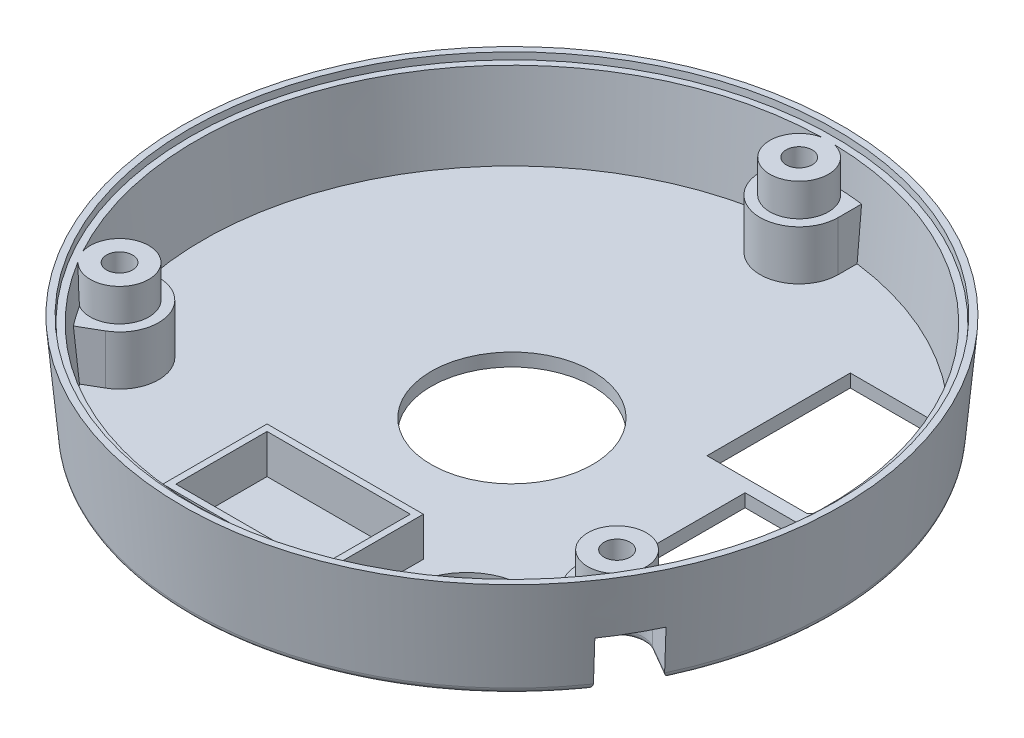
SolidWorks part; units mm, degrees
ref_plane "前视基准面" through (0, 0, 0) normal (0, 0, 1) x (1, 0, 0)
ref_plane "上视基准面" through (0, 0, 0) normal (0, 1, 0) x (1, 0, 0)
ref_plane "右视基准面" through (0, 0, 0) normal (1, 0, 0) x (0, 0, -1)
sketch "草图7" plane through (0, 0, 0) normal (0, 0, 1) x (1, 0, 0)
  line L0 (0, 0) -> (24.6, 0)
  line L1 (24.6, 0) -> (25.3, 7.8)
  line L2 (25.3, 7.8) -> (24.8, 7.8)
  line L3 (24.2551, 7.3) -> (23.6897, 1)
  line L4 (23.6897, 1) -> (0, 1)
  line L5 (0, 1) -> (0, 0)
  line L6 (24.8, 7.8) -> (24.7551, 7.3)
  line L7 (24.7551, 7.3) -> (24.2551, 7.3)
  dimension "D1" = 24.6
  dimension "D2" = 25.3
  dimension "D4" = 1
  dimension "D5" = 7.8
  dimension "D6" = 0.5
revolve "旋转1" add sketch "草图7" angle 360 about L5
sketch "草图8" plane through (0, 1, 0) normal (0, 1, 0) x (1, 0, 0)
  line L0 (-3, 22.05) -> (-3, 24.1141)
  line L1 (0, 22.05) -> (-19.0959, -11.025) construction
  line L2 (-19.0959, -11.025) -> (19.0959, -11.025) construction
  line L3 (19.0959, -11.025) -> (0, 22.05) construction
  line L4 (3, 22.05) -> (3, 24.1141)
  circle A0 centre (0, 0) radius 11.025 construction
  circle A1 centre (0, 22.05) radius 1
  circle A2 centre (0, 22.05) radius 2.25
  arc A3 (-3, 22.05) -> (3, 22.05) centre (0, 22.05) ccw
  circle A4 centre (0, 0) radius 24.3 construction
  arc A6 (-3, 24.1141) -> (3, 24.1141) centre (0, 0) cw
  dimension "D1" = 2
  dimension "D2" = 4.5
  dimension "D3" = 6
extrude "凸台-拉伸23" add sketch "草图8" along normal up to surface (6.3 mm away) contours A2 up to face at (-24.2551, 7.3, 0)
extrude "凸台-拉伸24" add sketch "草图8<4>" along normal blind 3.8 contours A6 L4 A3 L0
sketch "草图8<4>" plane through (0, 1, 0) normal (0, 1, 0) x (1, 0, 0) same geometry as "草图8"
extrude "切除-拉伸2" cut sketch "草图8<5>" against normal through all both and the other way through all contours A1
sketch "草图8<5>" plane through (0, 1, 0) normal (0, 1, 0) x (1, 0, 0) same geometry as "草图8"
pattern_circular "阵列(圆周)1" count 3 over 360 about axis through (0, 1, 0) along (0, 1, 0) of "凸台-拉伸23", "凸台-拉伸24", "切除-拉伸2"
sketch "草图9" plane through (0, 0, 0) normal (0, -1, 0) x (1, 0, 0)
  line L0 (2, -22.05) -> (2, -26.0952)
  line L1 (2, -26.0952) -> (-2, -26.0952)
  line L2 (-2, -26.0952) -> (-2, -22.05)
  arc A0 (2, -22.05) -> (-2, -22.05) centre (0, -22.05) ccw
  dimension "D1" = 4
extrude "切除-拉伸3" cut sketch "草图9" against normal blind 3.7 contours L2 A0 L0 L1
pattern_circular "阵列(圆周)2" count 3 over 360 about axis through (0, 0, 0) along (0, 1, 0) of "切除-拉伸3"
sketch "草图11" plane through (0, 1, 0) normal (0, 1, 0) x (1, 0, 0)
  line L0 (0, 0) -> (0, 22.05) construction
  line L1 (10, 15.975) -> (10, 4.975)
  line L2 (10, 4.975) -> (17.7, 4.975)
  line L4 (18.7, 5.975) -> (18.7, 14.975)
  line L6 (17.7, 15.975) -> (10, 15.975)
  line L7 (10, 15.975) -> (10, 21.4757) construction
  line L8 (13.9242, 3.975) -> (13.9242, -7.025)
  line L9 (13.9242, -7.025) -> (21.6242, -7.025)
  line L10 (22.6242, -6.025) -> (22.6242, 2.975)
  line L11 (21.6242, 3.975) -> (13.9242, 3.975)
  line L12 (19.0959, -8.025) -> (9.5, -8.025) construction
  line L15 (21.6242, -7.025) -> (22.6242, -6.025)
  line L16 (22.6242, 2.975) -> (21.6242, 3.975)
  line L17 (17.7, 4.975) -> (18.7, 5.975)
  line L18 (18.7, 14.975) -> (17.7, 15.975)
  arc A1 (21.8507, -9.1514) -> (3, 23.499) centre (0, 0) ccw construction
  arc A2 (20.5959, -8.4269) -> (17.5959, -13.6231) centre (19.0959, -11.025) ccw construction
  point P6 (22.6242, -7.025)
  point P7 (22.6242, 3.975)
  point P8 (0, 0)
  point P9 (0, 0)
  point P10 (18.7, 15.975)
  point P21 (18.7, 4.975)
  dimension "D1" = 10
  dimension "D2" = 8.7
  dimension "D3" = 11
  dimension "D4" = 1
  dimension "D5" = 1
  dimension "D7" = 8.7
  dimension "D8" = 11
extrude "切除-拉伸6" cut sketch "草图11" against normal up to surface (1 mm away) up to face at (0, 0, 0)
sketch "草图12" plane through (0, 1, 0) normal (0, 1, 0) x (1, 0, 0)
  line L0 (-5.5, -13.3) -> (-5.5, -20.3)
  line L1 (-5.5, -20.3) -> (5.5, -20.3)
  line L2 (5.5, -20.3) -> (5.5, -13.3)
  line L3 (5.5, -13.3) -> (-5.5, -13.3)
  line L4 (-18.1727, -25.3) -> (19.526, -25.3) construction
  circle A1 centre (0, 0) radius 25.3 construction
  point P3 (0, -13.3)
  dimension "D1" = 12
  dimension "D2" = 5
  dimension "D3" = 11
extrude "拉伸-薄壁1" add sketch "草图12" along normal blind 3 thin thin type one direction wall 0.5
sketch "草图13" plane through (0, 0, 0) normal (0, -1, 0) x (-1, 0, 0)
  line L0 (24.6, 19.236) -> (24.6, -17.3672) construction
  line L1 (6.6, 23.6981) -> (6.6, -23.6981) construction
  arc A0 (22.2337, -10.5272) -> (2, 24.5186) centre (0, 0) ccw construction
  arc A1 (-20.2337, -13.9913) -> (20.2337, -13.9913) centre (0, 0) ccw construction
  dimension "D1" = 18
sketch "草图14" plane through (0, 1, 0) normal (0, 1, 0) x (1, 0, 0)
  circle A0 centre (0, 0) radius 11.7 construction
  circle A2 centre (0, 0) radius 6.2
  circle A3 centre (11.7077, -15.2045) radius 4.5
  arc A4 (-18.8507, -14.3476) -> (18.8507, -14.3476) centre (0, 0) ccw construction
  point P6 (10.9576, -12.2246)
  point P7 (11.6858, -15.1761)
  dimension "D1" = 23.4
  dimension "D2" = 12.4
  dimension "D3" = 9
extrude "切除-拉伸7" cut sketch "草图14" against normal up to surface (1 mm away) up to face at (19.3908, 0, 1.525)
fillet "圆角1" radius 0.5 12 edges at (17.3638, 0, 10.025) (21.1648, 0, 9.9101) (-21.1648, 0, 9.9101) (-17.3638, 0, 10.025) (-19.1648, 0, 13.3742) (-21.3042, 0, -12.3) (-2, 0, -23.2843) (0, 0, -20.05) (2, 0, -23.2843) (21.3042, 0, -12.3) (19.1648, 0, 13.3742) (0, 0, 24.6)
